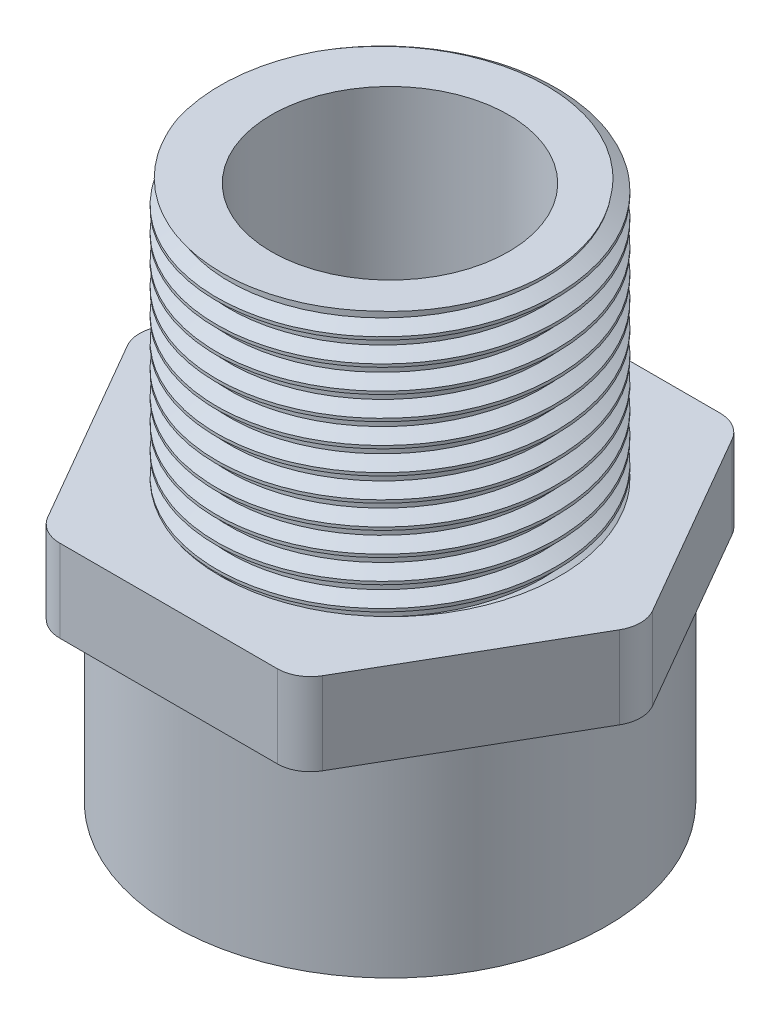
SolidWorks part; units mm, degrees
ref_plane "Front Plane" through (0, 0, 0) normal (0, 0, 1) x (1, 0, 0)
ref_plane "Top Plane" through (0, 0, 0) normal (0, 1, 0) x (1, 0, 0)
ref_plane "Right Plane" through (0, 0, 0) normal (1, 0, 0) x (0, 0, -1)
sketch "Sketch1" plane through (0, 0, 0) normal (0, 1, 0) x (1, 0, 0)
  circle A0 centre (0, 0) radius 16.6687
  dimension "D1" = 33.3375
extrude "Boss-Extrude1" add sketch "Sketch1" along normal blind 15.24
sketch "Sketch2" plane through (0, 15.24, 0) normal (0, 1, 0) x (1, 0, 0)
  line L1 (19.7057, 0) -> (9.8528, 17.0656)
  line L2 (9.8528, 17.0656) -> (-9.8528, 17.0656)
  line L3 (-9.8528, 17.0656) -> (-19.7057, 0)
  line L4 (-19.7057, 0) -> (-9.8528, -17.0656)
  line L5 (-9.8528, -17.0656) -> (9.8528, -17.0656)
  line L6 (9.8528, -17.0656) -> (19.7057, 0)
  circle A0 centre (0, 0) radius 17.0656 construction
  dimension "D1" = 34.1313
extrude "Boss-Extrude2" add sketch "Sketch2" along normal blind 6.35
sketch "Sketch3" plane through (0, 21.59, 0) normal (0, 1, 0) x (1, 0, 0)
  circle A0 centre (0, 0) radius 13.081
  dimension "D1" = 26.162
extrude "Boss-Extrude3" add sketch "Sketch3" along normal blind 19.685
thread "Thread1" pitch 1.8143 method cut profile "Thread Profile3" start angle 0, offset 3.54, length 0, pitch 1.8143, diameter 26.162
ref_plane "Plane3" through (-13.081, 44.815, 0) normal (0, 0, 1) x (-1, 0, 0)
sketch "Thread Profile3" plane through (-13.081, 44.815, 0) normal (0, 0, 1) x (-1, 0, 0)
  line L0 (0, 0) -> (0, 1.8143) construction
  line L11 (0, 0) -> (0, 1.5875)
  line L12 (0, 1.5875) -> (-0.982, 1.0205)
  line L13 (-0.982, 1.0205) -> (-0.982, 0.567)
  line L15 (-0.982, 0.567) -> (0, 0)
  line L17 (-0.982, 0.7937) -> (0, 0.7937) construction
  point P2 (0, 0)
  dimension "Pitch" = 1.8143
  dimension "Profile_Angle" = 60
  dimension "Profile_Land" = 0.4536
  dimension "Profile_Height" = 0.982
sketch "Sketch12" plane through (0, 41.275, 0) normal (0, 1, 0) x (1, 0, 0)
  circle A0 centre (0, 0) radius 9.144
  dimension "D1" = 18.288
extrude "Cut-Extrude1" cut sketch "Sketch12" against normal blind 21.4312
sketch "Sketch13" plane through (0, 0, 0) normal (0, -1, 0) x (1, 0, 0)
  circle A0 centre (0, 0) radius 13.4366
  dimension "D1" = 26.8732
extrude "Cut-Extrude2" cut sketch "Sketch13" against normal blind 19.8438
fillet "Fillet1" radius 2.54 6 edges at (-9.8528, 18.415, 17.0656) (9.8528, 18.415, 17.0656) (19.7057, 18.415, 0) (9.8528, 18.415, -17.0656) (-9.8528, 18.415, -17.0656) (-19.7057, 18.415, 0)
